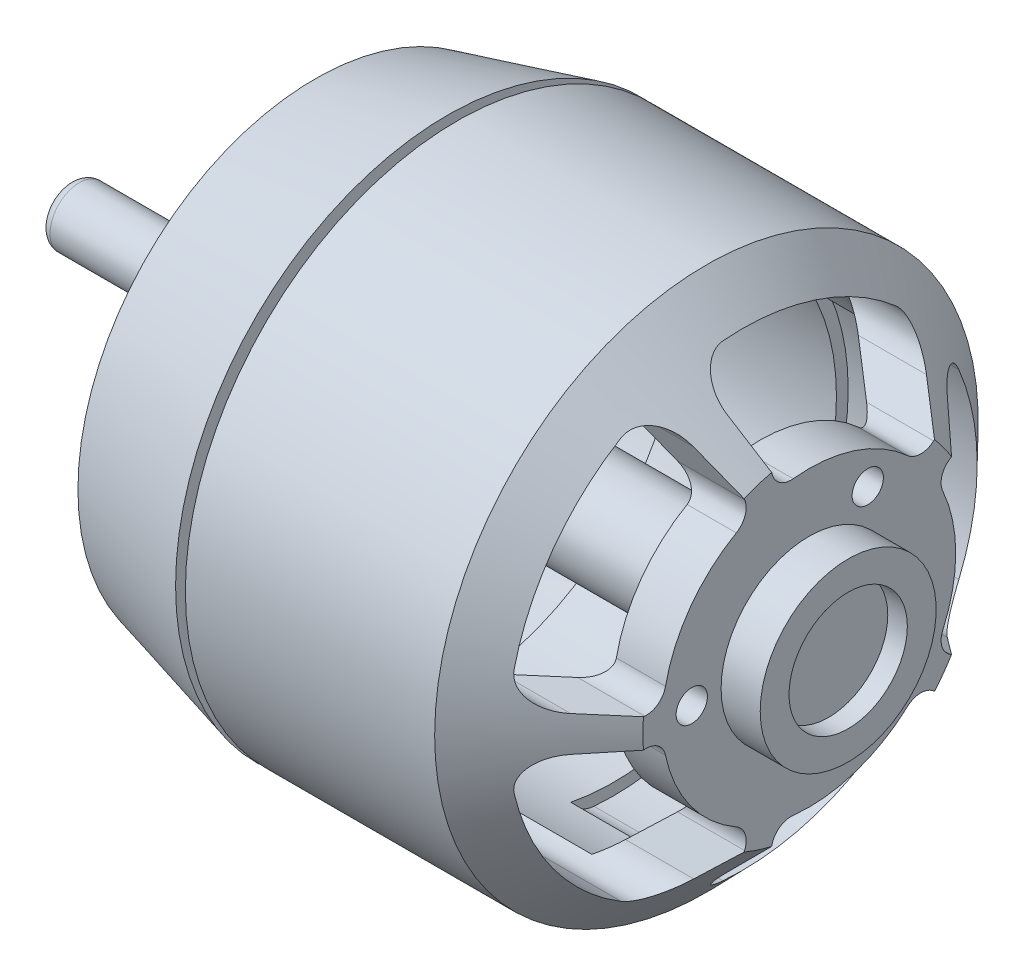
SolidWorks part; units mm, degrees
ref_plane "Front Plane" through (0, 0, 0) normal (0, 0, 1) x (1, 0, 0)
ref_plane "Top Plane" through (0, 0, 0) normal (0, 1, 0) x (1, 0, 0)
ref_plane "Right Plane" through (0, 0, 0) normal (1, 0, 0) x (0, 0, -1)
sketch "Sketch1" plane through (0, 0, 0) normal (0, 1, 0) x (1, 0, 0)
  line L0 (0, 0) -> (27.75, 0)
  line L1 (27.75, 0) -> (27.75, -4.5)
  line L2 (27.75, -4.5) -> (25.75, -4.5)
  line L3 (25.75, -4.5) -> (25.75, -8.5)
  line L4 (7.25, -13.9) -> (0, -12)
  line L5 (7.25, -12.9) -> (2, -11.5241)
  line L6 (7.75, -13.9) -> (20.5, -13.9)
  line L7 (20.5, -13.9) -> (25.75, -8.5)
  line L9 (0, -12) -> (0, -1.5)
  line L10 (7.75, -13.9) -> (7.75, -11.4)
  line L12 (23.25, -2.5) -> (23.25, -7.485)
  line L13 (19.4438, -11.4) -> (23.25, -7.485)
  line L14 (7.75, -11.4) -> (19.4438, -11.4)
  line L17 (2, -2.5) -> (23.25, -2.5)
  line L20 (7.25, -13.9) -> (7.25, -12.9)
  line L21 (2, -2.5) -> (2, -11.5241)
  line L22 (0, 0) -> (-12.07, 0)
  line L23 (-12.07, 0) -> (-12.07, -1.5)
  line L24 (-12.07, -1.5) -> (0, -1.5)
  dimension "D1" = 4.5
  dimension "D2" = 13.9
  dimension "D3" = 27.75
  dimension "D4" = 12.07
  dimension "D5" = 1.5
revolve "Revolve3" add sketch "Sketch1" angle 360 about L0
sketch "Sketch2" plane through (0, 0, 0) normal (1, 0, 0) x (0, 0, -1)
  line L0 (0, 0) -> (10.6066, 10.6066) construction
  line L1 (0, 0) -> (-4.9404, 4.9404) construction
  circle A0 centre (0, 0) radius 9 construction
  circle A1 centre (0, 9) radius 2.5
  circle A2 centre (-9, 0) radius 2.5
  circle A3 centre (9, 0) radius 2.5
  circle A4 centre (0, -9) radius 2.5
  circle A5 centre (0, 0) radius 9.5 construction
  circle A6 centre (0, 0) radius 8 construction
  circle A7 centre (5.6598, 5.6598) radius 1.25
  circle A8 centre (-5.6569, -5.6569) radius 1.25
  circle A9 centre (-6.7175, 6.7175) radius 1.25
  circle A10 centre (6.7175, -6.7175) radius 1.25
extrude "Cut-Extrude4" cut sketch "Sketch2" along normal blind 5 contours A1 | A2 | A9 | A7 | A8 | A4 | A3 | A10 region at (0, 9, 0) region at (0, 0, 9) region at (0, 0, -9) region at (0, -9, 0) region at (0, 5.6598, -5.6598) region at (0, -5.6569, 5.6569) region at (0, 6.7175, 6.7175) region at (0, -6.7175, -6.7175)
sketch "Sketch3" plane through (25.75, 0, 0) normal (1, 0, 0) x (0, 0, -1)
  line L0 (0, 0) -> (3.6969, 6.4032) construction
  line L1 (0, 0) -> (3.7407, -6.479) construction
  line L2 (0, 0) -> (7.3776, 0) construction
  line L3 (6.3705, 5.5378) -> (7.8432, 6.818)
  line L4 (-8.4089, 0.7357) -> (-10.3528, 0.9057)
  line L5 (-3.2982, 7.77) -> (-4.0606, 9.5662)
  line L6 (-1.8988, 8.2246) -> (-2.3378, 10.126)
  line L7 (7.2353, -4.3474) -> (8.9079, -5.3524)
  line L8 (7.2353, 4.3474) -> (8.9079, 5.3524)
  line L9 (-1.8988, -8.2246) -> (-2.3378, -10.126)
  line L10 (6.3705, -5.5378) -> (7.8432, -6.818)
  line L11 (-8.4089, -0.7357) -> (-10.3528, -0.9057)
  line L12 (-3.2982, -7.77) -> (-4.0606, -9.5662)
  circle A0 centre (0, 0) radius 6 construction
  circle A1 centre (-6, 0) radius 0.8
  circle A2 centre (3, 5.1962) radius 0.8
  circle A3 centre (3, -5.1962) radius 0.8
  arc A4 (-3.2982, 7.77) -> (-3.7223, 6.5111) centre (-4.2187, 7.3792) cw
  arc A5 (-8.4089, 0.7357) -> (-7.3427, 1.5281) centre (-8.3217, 1.7319) ccw
  arc A6 (-6.2187, 10.2629) -> (-11.6823, 2.7429) centre (0, 0) ccw
  arc A7 (-3.7223, 6.5111) -> (-7.3427, 1.5281) centre (0, 0) ccw
  arc A8 (-6.2187, 10.2629) -> (-4.0606, 9.5662) centre (-5.4414, 8.9801) cw
  arc A9 (-11.6823, 2.7429) -> (-10.3528, 0.9057) centre (-10.222, 2.4) ccw
  arc A10 (-1.0014, 11.9581) -> (-2.3378, 10.126) centre (-0.8762, 10.4634) ccw
  arc A11 (7.839, 9.0857) -> (-1.0014, 11.9581) centre (0, 0) ccw
  arc A12 (7.839, 9.0857) -> (7.8432, 6.818) centre (6.8591, 7.95) cw
  arc A13 (6.3705, 5.5378) -> (5.0421, 5.5522) centre (5.7144, 6.2925) cw
  arc A14 (5.0421, 5.5522) -> (-0.8157, 7.4555) centre (0, 0) ccw
  arc A15 (-1.8988, 8.2246) -> (-0.8157, 7.4555) centre (-0.9244, 8.4496) ccw
  arc A16 (11.0634, 4.6476) -> (8.9079, 5.3524) centre (9.6805, 4.0667) ccw
  arc A17 (11.0634, -4.6476) -> (11.0634, 4.6476) centre (0, 0) ccw
  arc A18 (11.0634, -4.6476) -> (8.9079, -5.3524) centre (9.6805, -4.0667) cw
  arc A19 (7.2353, -4.3474) -> (6.8386, -3.0796) centre (7.7504, -3.4903) cw
  arc A20 (6.8386, -3.0796) -> (6.8386, 3.0796) centre (0, 0) ccw
  arc A21 (7.2353, 4.3474) -> (6.8386, 3.0796) centre (7.7504, 3.4903) ccw
  arc A22 (7.839, -9.0857) -> (7.8432, -6.818) centre (6.8591, -7.95) ccw
  arc A23 (-1.0014, -11.9581) -> (7.839, -9.0857) centre (0, 0) ccw
  arc A24 (-1.0014, -11.9581) -> (-2.3378, -10.126) centre (-0.8762, -10.4634) cw
  arc A25 (-1.8988, -8.2246) -> (-0.8157, -7.4555) centre (-0.9244, -8.4496) cw
  arc A26 (-0.8157, -7.4555) -> (5.0421, -5.5522) centre (0, 0) ccw
  arc A27 (6.3705, -5.5378) -> (5.0421, -5.5522) centre (5.7144, -6.2925) ccw
  arc A28 (-6.2187, -10.2629) -> (-4.0606, -9.5662) centre (-5.4414, -8.9801) ccw
  arc A29 (-11.6823, -2.7429) -> (-6.2187, -10.2629) centre (0, 0) ccw
  arc A30 (-11.6823, -2.7429) -> (-10.3528, -0.9057) centre (-10.222, -2.4) cw
  arc A31 (-8.4089, -0.7357) -> (-7.3427, -1.5281) centre (-8.3217, -1.7319) cw
  arc A32 (-7.3427, -1.5281) -> (-3.7223, -6.5111) centre (0, 0) ccw
  arc A33 (-3.2982, -7.77) -> (-3.7223, -6.5111) centre (-4.2187, -7.3792) ccw
  point P78 (0, 0)
  dimension "D1" = 1
  dimension "D2" = 1.5
  dimension "D3" = 5
extrude "Cut-Extrude5" cut sketch "Sketch3" against normal blind 10
fillet "Fillet1" radius 0.5 1 edges at (-12.07, 0, 1.5)
chamfer "Chamfer1" distance 0.5 angle 45 1 edges at (0, 0, 12) first distance on face at (7.25, 0, 13.9)
sketch "Sketch4" plane through (27.75, 0, 0) normal (1, 0, 0) x (0, 0, -1)
  circle A0 centre (0, 0) radius 3.025
  dimension "D1" = 6.05
extrude "Cut-Extrude6" cut sketch "Sketch4" against normal blind 1
